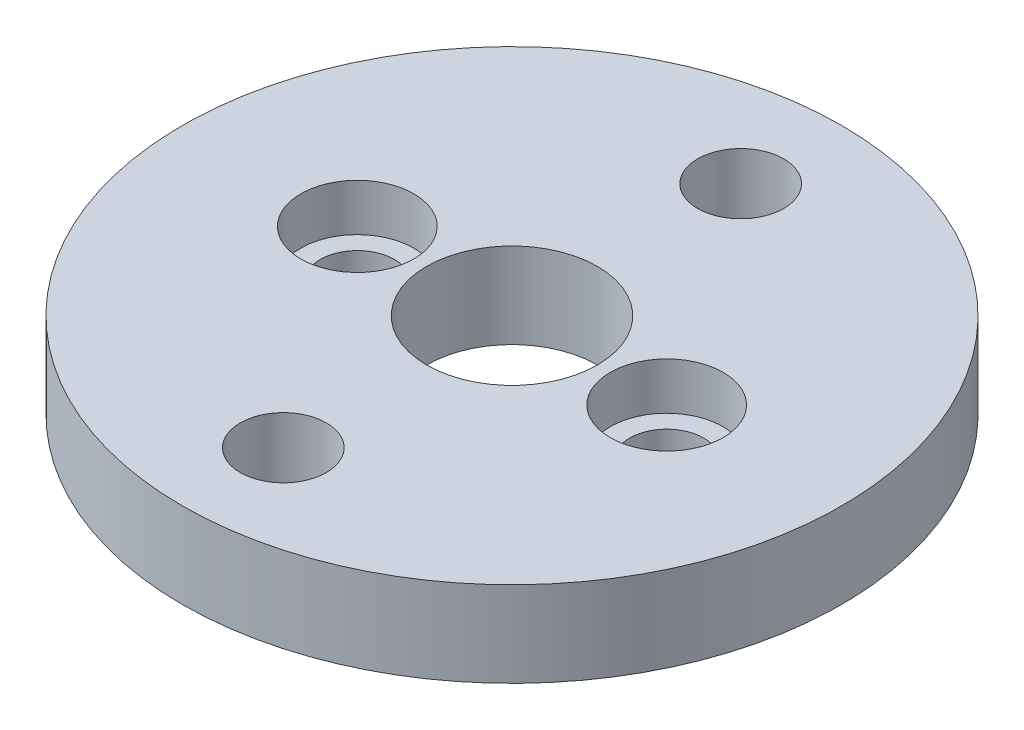
SolidWorks part; units mm, degrees
ref_plane "Front Plane" through (0, 0, 0) normal (0, 0, 1) x (1, 0, 0)
ref_plane "Top Plane" through (0, 0, 0) normal (0, 1, 0) x (1, 0, 0)
ref_plane "Right Plane" through (0, 0, 0) normal (1, 0, 0) x (0, 0, -1)
sketch "Sketch1" plane through (0, 0, 0) normal (0, 1, 0) x (1, 0, 0)
  circle A0 centre (0, 0) radius 12.25
  dimension "D1" = 24.5
extrude "Boss-Extrude1" add sketch "Sketch1" along normal blind 3.175 contours A0
sketch "Sketch2" plane through (0, 0, 0) normal (0, -1, 0) x (1, 0, 0)
  line L0 (0, 8.5) -> (0, -8.5) construction
  line L1 (5.75, 0) -> (-5.75, 0) construction
  circle A0 centre (0, 0) radius 3.175
  circle A1 centre (0, 8.5) radius 1.6
  circle A2 centre (0, -8.5) radius 1.6
  circle A3 centre (-5.75, 0) radius 1.375
  circle A4 centre (5.75, 0) radius 1.375
  point P4 (0, 0)
  point P8 (0, 0)
  dimension "D2" = 6.35
  dimension "D3" = 3.2
  dimension "D5" = 2.75
  dimension "D1" = 17
  dimension "D4" = 11.5
extrude "Cut-Extrude1" cut sketch "Sketch2" against normal up to next
sketch "Sketch3" plane through (0, 3.175, 0) normal (0, 1, 0) x (1, 0, 0)
  circle A0 centre (-5.75, 0) radius 2.1
  circle A1 centre (5.75, 0) radius 2.1
  dimension "D1" = 4.2
extrude "Cut-Extrude2" cut sketch "Sketch3" against normal blind 1.75
